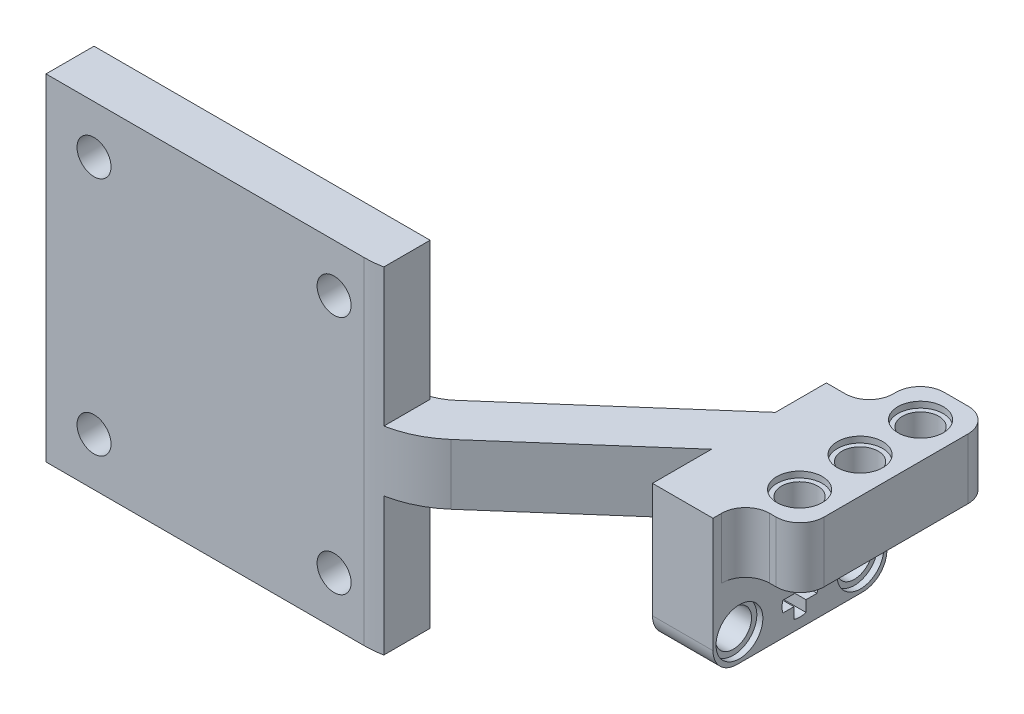
SolidWorks part; units mm, degrees
ref_plane "Front Plane" through (0, 0, 0) normal (0, 0, 1) x (1, 0, 0)
ref_plane "Top Plane" through (0, 0, 0) normal (0, 1, 0) x (1, 0, 0)
ref_plane "Right Plane" through (0, 0, 0) normal (1, 0, 0) x (0, 0, -1)
sketch "Sketch6" plane through (0, 0, 0) normal (0, 1, 0) x (1, 0, 0)
  line L1 (-4.7625, 12.7) -> (4.7625, 12.7)
  line L2 (-4.7625, 12.7) -> (-4.7625, -12.7)
  line L3 (-4.7625, -12.7) -> (4.7625, -12.7)
  line L4 (4.7625, 12.7) -> (4.7625, -12.7)
  line L5 (-4.7625, 12.7) -> (4.7625, -12.7) construction
  line L6 (-4.7625, -12.7) -> (4.7625, 12.7) construction
  point P0 (0, 0)
  dimension "D1" = 9.525
  dimension "D2" = 25.4
extrude "Boss-Extrude1" add sketch "Sketch6" against normal blind 8
sketch "Sketch16" plane through (0, 0, 0) normal (0, -1, 0) x (1, 0, 0)
  line L1 (-2.4423, -5.9876) -> (-10.4423, -5.9876)
  line L2 (-2.4423, -5.9876) -> (-2.4423, 17.0124)
  line L3 (-2.4423, 17.0124) -> (-10.4423, 17.0124)
  line L4 (-10.4423, -5.9876) -> (-10.4423, 17.0124)
  line L5 (-2.4423, -5.9876) -> (-10.4423, 17.0124) construction
  line L6 (-2.4423, 17.0124) -> (-10.4423, -5.9876) construction
  line L7 (-4.7625, -12.7) -> (-4.7625, 12.7) construction
  point P0 (-6.4423, 5.5124)
  point P12 (-4.7625, 0)
  dimension "D1" = 6.4423
  dimension "D2" = 5.5124
  dimension "D3" = 8
  dimension "D4" = 23
extrude "Boss-Extrude6" add sketch "Sketch16" along normal up to surface (8 mm away) up to face at (0, -8, 0)
sketch "Sketch7" plane through (0, 0, 0) normal (0, 1, 0) x (1, 0, 0)
  circle A0 centre (0, 8) radius 2.4
  circle A1 centre (0, 0) radius 2.4
  circle A2 centre (0, -8) radius 2.4
  circle A3 centre (0, 8) radius 3
  circle A4 centre (0, 0) radius 3
  circle A5 centre (0, -8) radius 3
  dimension "D3" = 4.8
  dimension "D1" = 8
  dimension "D2" = 8
  dimension "D4" = 0.6
extrude "Cut-Extrude1" cut sketch "Sketch7" against normal blind 0.8
extrude "Cut-Extrude2" cut sketch "Sketch7<3>" against normal blind 7.2 contours A0 | A1 | A2 region at (0, 0, -8) region at (0, 0, 0) region at (0, 0, 8)
sketch "Sketch7<3>" plane through (0, 0, 0) normal (0, 1, 0) x (1, 0, 0) same geometry as "Sketch7"
sketch "Sketch9" plane through (0, -7.2, -7.2) normal (0, 1, 0) x (1, 0, 0)
  circle A0 centre (0, 0.8) radius 2.4
  circle A1 centre (0, -7.2) radius 2.4
  circle A2 centre (0, -15.2) radius 2.4
  circle A3 centre (0, 0.8) radius 3
  circle A4 centre (0, -7.2) radius 3
  circle A5 centre (0, -15.2) radius 3
  dimension "D3" = 4.8
  dimension "D1" = 8
  dimension "D2" = 8
  dimension "D4" = 0.6
extrude "Cut-Extrude4" cut sketch "Sketch9" against normal blind 0.8 contours A3 | A4 | A5
ref_plane "Plane4" through (0, 0, 28.448) normal (0, 0, 1) x (1, 0, 0)
sketch "Sketch10" plane through (0, -8, 0) normal (0, -1, 0) x (-1, 0, 0)
  line L1 (4.7625, 4.2239) -> (34.7625, -22.098)
  line L2 (4.7625, 4.2239) -> (4.7625, -4.2239) construction
  line L3 (34.7625, -22.098) -> (60.1625, -22.098)
  line L4 (60.1625, -22.098) -> (60.1625, -28.448)
  line L5 (-57.9984, -28.448) -> (57.9984, -28.448) construction
  line L8 (4.7625, -4.2239) -> (32.3717, -28.448)
  line L10 (4.7625, 4.2239) -> (4.7625, -4.2239)
  line L14 (4.7625, 12.7) -> (4.7625, 5.9876) construction
  line L18 (32.3717, -28.448) -> (60.1625, -28.448)
  point P2 (4.7625, 0)
  point P3 (4.7625, -4.8745)
  dimension "D1" = 30
  dimension "D2" = 6.35
  dimension "D3" = 25.4
  dimension "D4" = 6.35
extrude "Boss-Extrude3" add sketch "Sketch10" against normal up to surface (8 mm away) up to face at (0, 0, -5)
fillet "Fillet1" radius 3.175 2 edges at (-4.7625, -4, -5.9876) (-2.4423, -4, 12.7)
fillet "Fillet3" radius 3.175 3 edges at (4.7625, -4, -12.7) (4.7625, -4, 12.7) (-4.7625, -4, -12.7)
sketch "Sketch18" plane through (0, 0, 0) normal (0, 1, 0) x (1, 0, 0)
  line L0 (-57.9984, -28.448) -> (57.9984, -28.448) construction
  line L1 (-79.2125, -22.098) -> (-34.7625, -22.098)
  line L2 (-79.2125, -22.098) -> (-79.2125, -28.448)
  line L3 (-79.2125, -28.448) -> (-34.7625, -28.448)
  line L4 (-34.7625, -22.098) -> (-34.7625, -28.448)
  point P7 (-60.1625, -22.098)
  point P8 (-38.4145, -28.448)
  point P9 (0, 0)
  dimension "D1" = 44.45
extrude "Boss-Extrude7" add sketch "Sketch18" along normal blind 18.225 and the other way blind 26.225
fillet "Fillet6" radius 12.7 1 edges at (-32.3717, -4, 28.448)
fillet "Fillet7" radius 6.35 1 edges at (-34.7625, -4, 22.098)
sketch "Sketch11" plane through (0, -8, 0) normal (0, -1, 0) x (-1, 0, 0)
  line L1 (10.4422, -17.0124) -> (2.4422, -17.0124)
  line L2 (10.4422, -17.0124) -> (10.4422, 5.9876)
  line L3 (10.4422, 5.9876) -> (2.4422, 5.9876)
  line L4 (2.4422, -17.0124) -> (2.4422, 5.9876)
  line L5 (10.4422, -17.0124) -> (2.4422, 5.9876) construction
  line L6 (10.4422, 5.9876) -> (2.4422, -17.0124) construction
  point P0 (6.4422, -5.5124)
  dimension "D1" = 6.4422
  dimension "D3" = 8
  dimension "D4" = 23
  dimension "D5" = 5.5124
extrude "Boss-Extrude4" add sketch "Sketch11" along normal blind 6.7462 contours L4 L3 L2 L1
sketch "Sketch13" plane through (-2.4423, 0, 0) normal (1, 0, 0) x (0, 0, -1)
  line L0 (-17.0124, -14.7462) -> (5.9876, -14.7462) construction
  line L1 (-6.3124, -14.0148) -> (-6.3124, -12.5521)
  line L2 (-4.7124, -12.5521) -> (-4.7124, -14.0148)
  line L3 (-6.3124, -14.0148) -> (-4.7124, -14.0148) construction
  line L4 (-6.3124, -14.0148) -> (-6.3124, -15.4775) construction
  line L5 (-6.3124, -14.0148) -> (-7.7751, -14.0148)
  line L6 (-7.7751, -15.4775) -> (-6.3124, -15.4775)
  line L7 (-6.3124, -15.4775) -> (-6.3124, -16.9403)
  line L8 (-4.7124, -16.9403) -> (-4.7124, -15.4775)
  line L9 (-4.7124, -15.4775) -> (-3.2496, -15.4775)
  line L10 (-4.7124, -14.0148) -> (-3.2496, -14.0148)
  line L11 (-3.2496, -14.0148) -> (-5.9183, -14.0148)
  circle A0 centre (-5.5124, -14.7462) radius 2.5157 construction
  circle A1 centre (-13.5124, -14.7462) radius 3.1
  circle A2 centre (2.4876, -14.7462) radius 3.1
  circle A3 centre (-13.5124, -14.7462) radius 2.4
  circle A4 centre (2.4876, -14.7462) radius 2.4
  arc A5 (-6.3124, -12.5521) -> (-4.7124, -12.5521) centre (-5.5124, -15.0259) cw
  arc A6 (-7.7751, -14.0148) -> (-7.7751, -15.4775) centre (-5.2801, -14.7462) ccw
  arc A7 (-6.3124, -16.9403) -> (-4.7124, -16.9403) centre (-5.5124, -14.4664) ccw
  arc A8 (-3.2496, -14.0148) -> (-3.2496, -15.4775) centre (-5.7446, -14.7462) cw
  point P14 (-5.5124, -14.0148)
  point P16 (-6.3124, -14.7462)
  line M4 (-17.0124, -14.7462) -> (5.9876, -14.7462)
  dimension "D1" = 6.2
  dimension "D2" = 4.8
  dimension "D7" = 2.6
  dimension "D3" = 8
  dimension "D4" = 8
  dimension "D5" = 1.4627
  dimension "D6" = 1.6
sketch "Sketch14" plane through (0, -14.7462, 0) normal (0, -1, 0) x (-1, 0, 0)
  line L1 (10.4422, -17.0124) -> (2.4422, -17.0124)
  line L2 (10.4422, -17.0124) -> (10.4422, 5.9876)
  line L3 (10.4422, 5.9876) -> (2.4422, 5.9876)
  line L4 (2.4422, -17.0124) -> (2.4422, 5.9876)
extrude "Boss-Extrude5" add sketch "Sketch14" along normal blind 3.6 contours L2 L3 L4 L1
extrude "Cut-Extrude5" cut sketch "Sketch13" against normal blind 0.8 contours A3 A1 M4 | A3 A1 M4 | A8 A6 L6 L7 A7 L8 L9 M4 | A8 L10 L2 A5 L1 L5 A6 M4 | A4 A2 M4 | A4 A2 M4 region at (-2.4423, -11.7155, -2.4876) region at (-2.4423, -14.8155, 0.2624) region at (-2.4423, -17.7768, 13.5124) region at (-2.4423, -14.6768, 10.7624) region at (-2.4423, -13.9029, 5.5124) region at (-2.4423, -15.5895, 5.5124)
extrude "Cut-Extrude6" cut sketch "Sketch13<3>" against normal through all contours A8 A6 L6 L7 A7 L8 L9 M4 | A8 L10 L2 A5 L1 L5 A6 M4 | A4 M4 | A4 M4 | A3 region at (-2.4423, -13.9029, 5.5124) region at (-2.4423, -15.5895, 5.5124) region at (-2.4423, -15.7648, -2.4876) region at (-2.4423, -13.7276, -2.4876)
sketch "Sketch13<3>" plane through (-2.4423, 0, 0) normal (1, 0, 0) x (0, 0, -1) same geometry as "Sketch13"
ref_plane "Plane5" through (-6.4423, 0, 0) normal (1, 0, 0) x (0, 0, -1)
mirror "Mirror1" about plane through (-6.4423, 0, 0) normal (1, 0, 0) of "Cut-Extrude5"
hole_wizard "#8 Clearance Hole1" positions "Sketch19" profile "Sketch20" hole size "#8" standard "ANSI Inch" end condition through all
sketch "Sketch19" plane through (0, 0, 22.098) normal (0, 0, -1) x (-1, 0, 0)
  line L0 (34.7625, 0) -> (34.7625, 18.225) construction
  line L1 (34.7625, 18.225) -> (79.2125, 18.225) construction
  line L3 (34.7625, -26.225) -> (79.2125, -26.225) construction
  line L4 (79.2125, -26.225) -> (79.2125, 18.225) construction
  point P0 (72.8625, 11.875)
  point P2 (41.1125, 11.875)
  point P4 (41.1125, -19.875)
  point P6 (72.8625, -19.875)
  dimension "D1" = 6.35
  dimension "D2" = 6.35
  dimension "D3" = 6.35
  dimension "D4" = 6.35
sketch "Sketch20" plane through (-72.8625, 11.875, 22.098) normal (1, 0, 0) x (0, 1, 0)
  line L0 (0, 0) -> (0, 6.35)
  line L1 (0, 6.35) -> (2.2479, 6.35)
  line L2 (2.2479, 6.35) -> (2.2479, 0)
  line L5 (2.2479, 0) -> (0, 0)
  line L11 (0, -6.35) -> (0, 107.95) construction
  dimension "Thru Hole Dia." = 4.4958
  dimension "Thru Hole Depth" = 6.35
fillet "Fillet8" radius 3.175 2 edges at (-6.4422, -18.3462, 17.0124) (-6.4422, -18.3462, -5.9876) tangent propagation no
